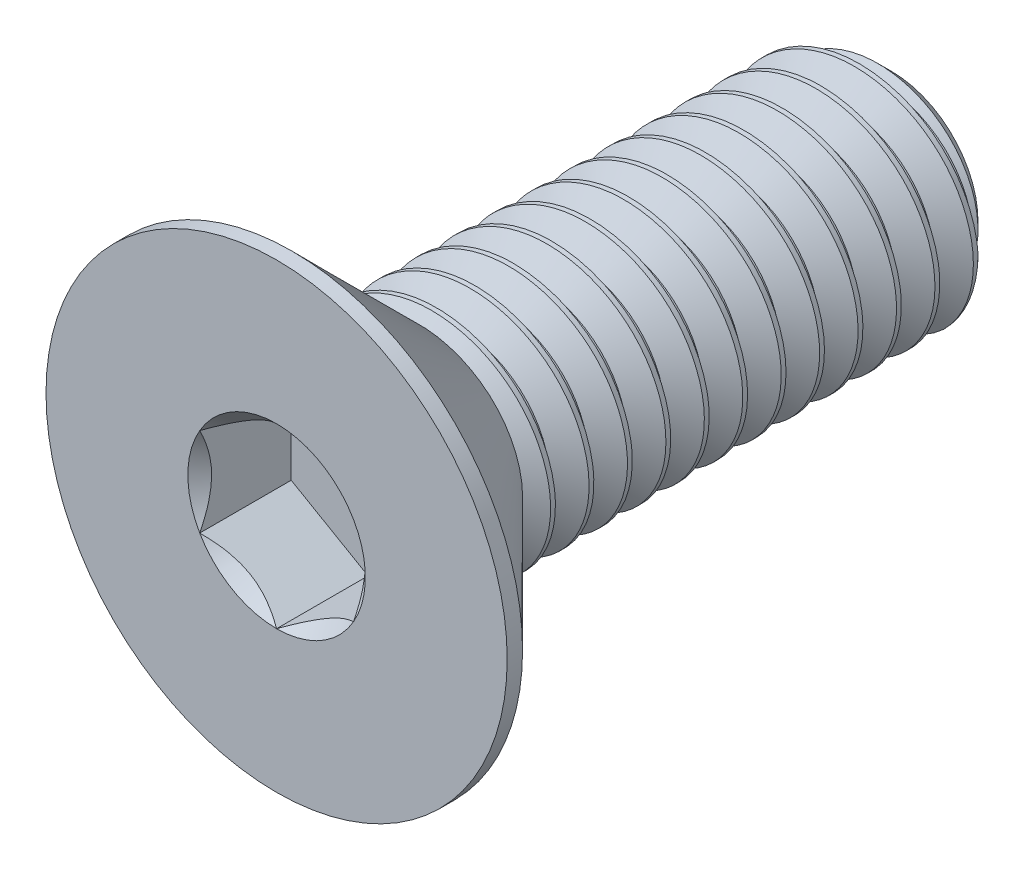
SolidWorks part; units mm, degrees
ref_plane "Front" through (0, 0, 0) normal (0, 0, 1) x (1, 0, 0)
ref_plane "Top" through (0, 0, 0) normal (0, 1, 0) x (1, 0, 0)
ref_plane "Right" through (0, 0, 0) normal (1, 0, 0) x (0, 0, -1)
sketch "Sketch1" plane through (0, 0, 0) normal (1, 0, 0) x (0, 0, -1)
  line L0 (0, 3) -> (0.2, 3) construction
  line L1 (0.2, 3) -> (1.7, 1.5) construction
  line L2 (0, 1.5) -> (8, 1.5)
  line L3 (8, 1.5) -> (8, 0)
  line L4 (8, 0) -> (0, 0)
  line L5 (0, 0) -> (0, 3) construction
  line L6 (0, 3) -> (0, -3) construction
  line L7 (8, 1.5) -> (8, -1.5) construction
  line L8 (0, -3) -> (0.2, -3) construction
  line L9 (0.2, -3) -> (1.7, -1.5) construction
  line L11 (0, 1.5) -> (0, 0)
  line L12 (1.7, 1.5) -> (1.7, 0) construction
revolve "Revolve1" add sketch "Sketch1" angle 360 mid plane about L4
sketch "Sketch3" plane through (0, 0, -8) normal (0, 0, -1) x (-1, 0, 0)
  circle A0 centre (0, 0) radius 1.5
curve "Helix/Spiral1" pitch 0.5 height 8 radius 1.5 centre (0, 0, -8) axis (0, 0, 1) start towards (0, 1, 0)
sketch "Sketch2" plane through (0, 0, 0) normal (1, 0, 0) x (0, 0, -1)
  line L0 (8, 1.5) -> (8.4375, 1.5)
  line L1 (8.4375, 1.5) -> (8.25, 1.1752)
  line L2 (8.25, 1.1752) -> (8.1875, 1.1752)
  line L3 (8.1875, 1.1752) -> (8, 1.5)
  line L4 (8.0938, 1.3376) -> (8.3438, 1.3376) construction
  dimension "D1" = 60
  dimension "D2" = 0.0625
  dimension "D3" = 0.25
chamfer "Chamfer1" distance 0.375 angle 45 1 edges at (0, 1.5, -8)
sweep "Cut-Sweep1" cut profiles "Sketch2" path "Helix/Spiral1" align with end faces yes
sketch "Sketch7" plane through (0, 0, 0) normal (1, 0, 0) x (0, 0, -1)
  line L0 (0, 3) -> (0.2, 3) construction
  line L1 (0.2, 3) -> (1.7, 1.5) construction
  line L2 (0, 3) -> (0.2, 3)
  line L3 (0.2, 3) -> (1.7, 1.5)
  line L4 (1.7, 1.5) -> (1.7, 0) construction
  line L5 (1.7, 1.5) -> (1.7, 0)
  line L7 (0, 0) -> (0, 3) construction
  line L8 (0, 0) -> (0, 3)
  line L9 (0, 0) -> (1.7, 0)
  line L10 (3.3, 0) -> (-3.3, 0) construction
revolve "Revolve2" add sketch "Sketch7" angle 360 mid plane about L9
ref_plane "Plane1" through (0, 0, -1.7) normal (0, 0, 1) x (1, 0, 0)
sketch "Sketch8" plane through (0, 0, -1.7) normal (0, 0, 1) x (1, 0, 0)
  circle A0 centre (0, 0) radius 1.5
extrude "Boss-Extrude1" add sketch "Sketch8" against normal through all draft 45
sketch "Sketch5" plane through (0, 0, 0) normal (0, 0, 1) x (1, 0, 0)
  line L1 (1, -0.5774) -> (1, 0.5774)
  line L2 (1, 0.5774) -> (0, 1.1547)
  line L3 (0, 1.1547) -> (-1, 0.5774)
  line L4 (-1, 0.5774) -> (-1, -0.5774)
  line L5 (-1, -0.5774) -> (0, -1.1547)
  line L6 (0, -1.1547) -> (1, -0.5774)
  circle A0 centre (0, 0) radius 1 construction
  dimension "Hex" = 2
extrude "Cut-Extrude2" cut sketch "Sketch5" against normal blind 1.19
sketch "Sketch6" plane through (0, 0, 0) normal (0, 0, 1) x (1, 0, 0)
  circle A0 centre (0, 0) radius 1.1547
extrude "Cut-Extrude3" cut sketch "Sketch6" against normal blind 1.19 draft 45
sketch "Sketch9" [suppressed] plane through (0, 0, -5.5) normal (0, 0, 1) x (1, 0, 0)
  circle A1 centre (0, 0) radius 5
  circle A2 centre (0, 0) radius 5
  point P0 (0, 5)
  dimension "D1" = 0
extrude "Boss-Extrude2" [suppressed] add sketch "Sketch9" against normal offset from surface (18.5 mm away) 26 up to face at (0, 1.125, -8)
fillet "Fillet1" [suppressed] radius 0.3
sketch "Sketch10" plane through (0, 0, 0) normal (1, 0, 0) x (0, 0, -1)
  line L0 (8, 1.5) -> (8, -1.5) construction
  point P0 (7.25, -1.5)
  dimension "D1" = 0.75
equation "\"D3@Helix/Spiral1\" = \"Lg@Sketch1\""
equation "\"D2@Sketch2\" = \"D4@Helix/Spiral1\" * .125"
equation "\"D3@Sketch2\" = \"D4@Helix/Spiral1\" * .5"
equation "\"D1@Chamfer1\" = \"D4@Helix/Spiral1\" * .75"
equation "\"D1@Cut-Extrude2\" = \"Head Ht@Sketch1\" * .7"
equation "\"D1@Sketch10\" = \"D4@Helix/Spiral1\" * 1.5"
equation "\"D1@Cut-Extrude3\" = \"D1@Cut-Extrude2\""
equation "\"D1@Fillet1\" = \"Dia@Sketch1\" * .1"
